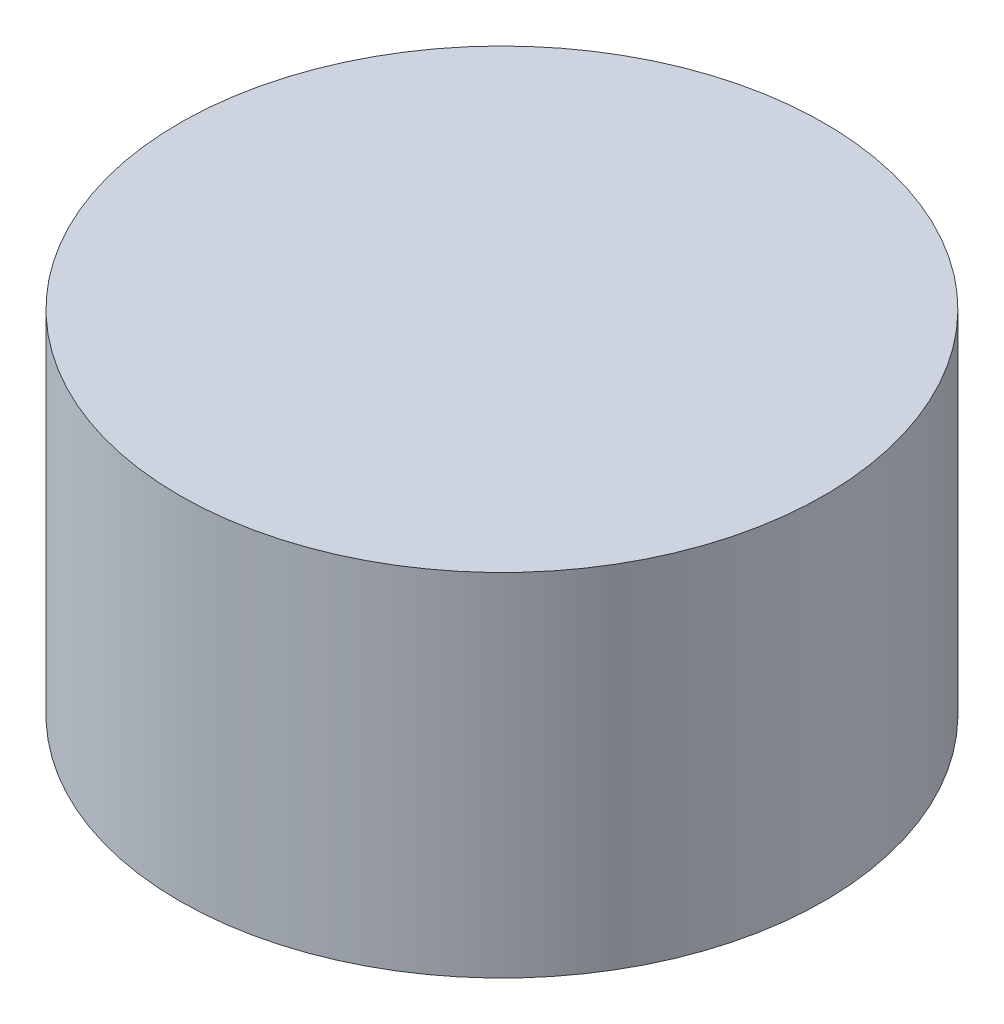
SolidWorks part; units mm, degrees
ref_plane "Front Plane" through (0, 0, 0) normal (0, 0, 1) x (1, 0, 0)
ref_plane "Top Plane" through (0, 0, 0) normal (0, 1, 0) x (1, 0, 0)
ref_plane "Right Plane" through (0, 0, 0) normal (1, 0, 0) x (0, 0, -1)
sketch "Sketch1" plane through (0, 0, 0) normal (0, 1, 0) x (1, 0, 0)
  circle A0 centre (0, 0) radius 280
  circle A1 centre (0, 0) radius 275
  dimension "D1" = 560
  dimension "D2" = 550
extrude "Boss-Extrude1" add sketch "Sketch1" along normal blind 300
sketch "Sketch2" plane through (0, 300, 0) normal (0, 1, 0) x (1, 0, 0)
  circle A0 centre (0, 0) radius 280
extrude "Boss-Extrude2" add sketch "Sketch2" along normal blind 5
